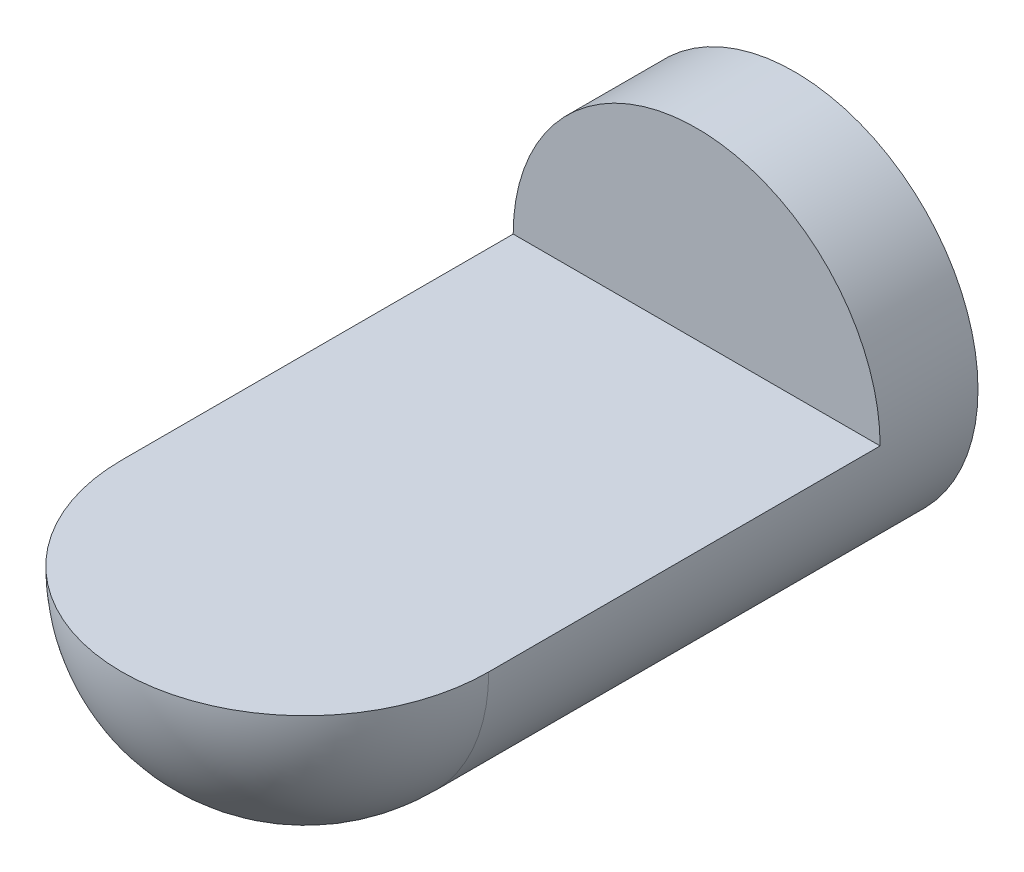
SolidWorks part; units mm, degrees
ref_plane "Front Plane" through (0, 0, 0) normal (0, 0, 1) x (1, 0, 0)
ref_plane "Top Plane" through (0, 0, 0) normal (0, 1, 0) x (1, 0, 0)
ref_plane "Right Plane" through (0, 0, 0) normal (1, 0, 0) x (0, 0, -1)
sketch "Sketch1" plane through (0, 0, 0) normal (1, 0, 0) x (0, 0, -1)
  line L0 (-146.9091, 0) -> (313.5945, 0) construction
  line L1 (200, 0) -> (-75, 0)
  line L2 (200, 0) -> (200, 75)
  line L3 (0, 75) -> (200, 75)
  arc A0 (-75, 0) -> (0, 75) centre (0, 0) cw
  dimension "D1" = 75
  dimension "D2" = 200
revolve "Revolve1" add sketch "Sketch1" angle 360 about L0
sketch "Sketch2" plane through (0, 0, 0) normal (1, 0, 0) x (0, 0, -1)
  line L0 (-88.0407, 0) -> (120.4455, 0) construction
  line L1 (160, 0) -> (160, 75)
  line L2 (200, 75) -> (0, 75) construction
  line L3 (160, 0) -> (-75, 0)
  line L4 (160, 75) -> (0, 75)
  line L5 (200, -75) -> (200, 75) construction
  arc A0 (0, 75) -> (0, -75) centre (0, 0) ccw construction
  arc A1 (-75, 0) -> (0, 75) centre (0, 0) cw
  dimension "D1" = 40
extrude "Cut-Extrude1" cut sketch "Sketch2" along normal through all and the other way through all
ref_axis "Axis1" through (0, 82.5, 0) along (0, -1, 0)
ref_axis "Axis2" through (0, 0, -213.75) along (0, 0, 1)
equation "\"link5_diameter\"=150"
equation "\"D1@Sketch1\"=\"link5_diameter\"/2"
equation "\"link5_length\"=200"
equation "\"D2@Sketch1\"=\"link5_length\""
equation "\"base_link_length\"=150"
equation "\"link1_diameter\"=150"
equation "\"link1_length\"=150"
equation "\"link2_diameter\"=150"
equation "\"link2_length\"=300"
equation "\"link3_diameter\"=150"
equation "\"link3_length\"=150"
equation "\"link4_diameter\"=150"
equation "\"link4_length\"=150"
equation "\"end_effector_diameter\"=150"
equation "\"end_effector_length\"=150"
equation "\"base_link_diameterA\"=200"
equation "\"base_link_diameterB\"=150"
equation "\"base_link_lengthA\"=50"
equation "\"base_link_diameter\"=75"
